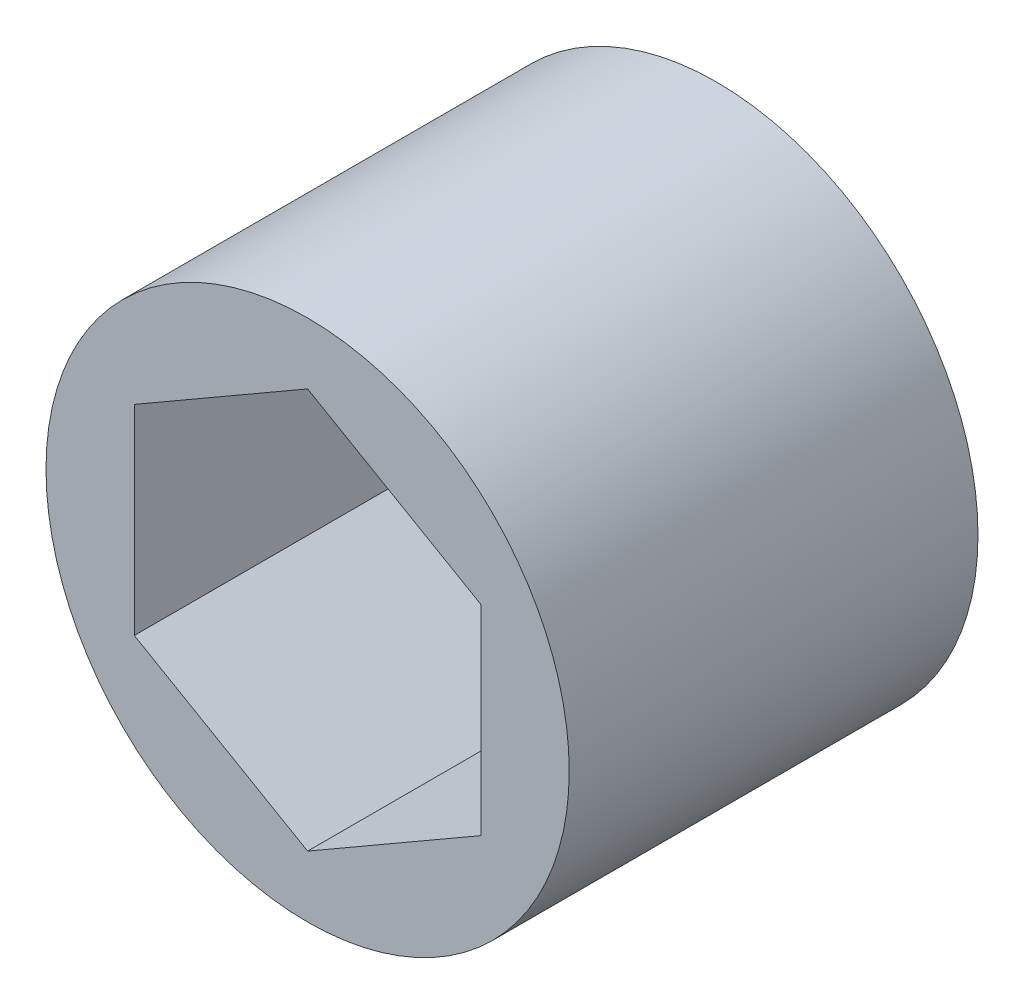
SolidWorks part; units mm, degrees
material "Nylon 101"
ref_plane "Front Plane" through (0, 0, 0) normal (0, 0, 1) x (1, 0, 0)
ref_plane "Top Plane" through (0, 0, 0) normal (0, 1, 0) x (1, 0, 0)
ref_plane "Right Plane" through (0, 0, 0) normal (1, 0, 0) x (0, 0, -1)
sketch "Sketch3" plane through (0, 0, 0) normal (0, 0, 1) x (1, 0, 0)
  line L1 (0, 7.7723) -> (-6.731, 3.8861)
  line L2 (-6.731, 3.8861) -> (-6.731, -3.8861)
  line L3 (-6.731, -3.8861) -> (0, -7.7723)
  line L4 (0, -7.7723) -> (6.731, -3.8861)
  line L5 (6.731, -3.8861) -> (6.731, 3.8861)
  line L6 (6.731, 3.8861) -> (0, 7.7723)
  circle A0 centre (0, 0) radius 10.16
  circle A1 centre (0, 0) radius 6.731 construction
  dimension "D1" = 13.462
  dimension "D2" = 20.32
extrude "Boss-Extrude1" add sketch "Sketch3" along normal mid plane 15.875
